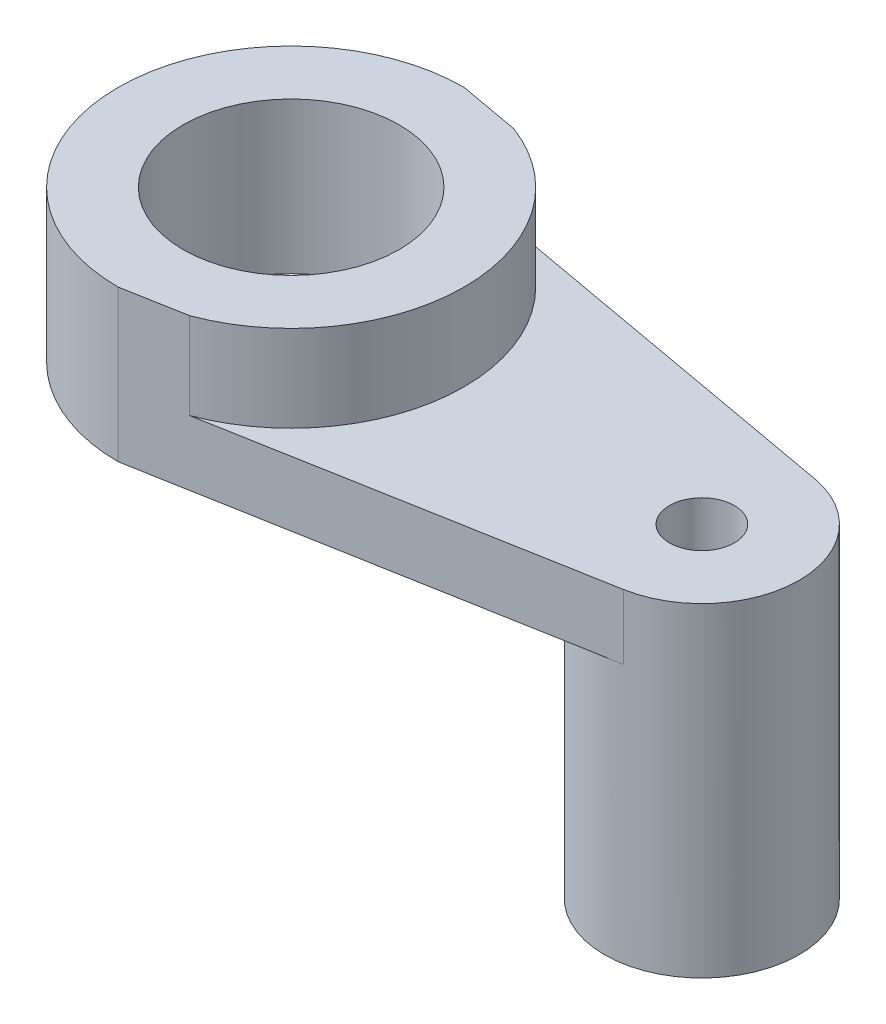
SolidWorks part; units mm, degrees
ref_plane "Front Plane" through (0, 0, 0) normal (0, 0, 1) x (1, 0, 0)
ref_plane "Top Plane" through (0, 0, 0) normal (0, 1, 0) x (1, 0, 0)
ref_plane "Right Plane" through (0, 0, 0) normal (1, 0, 0) x (0, 0, -1)
sketch "Sketch1" plane through (0, 0, 0) normal (0, 1, 0) x (1, 0, 0)
  line L0 (0, 0) -> (38, 0)
  line L1 (0, -16) -> (39.5977, -8.8571)
  line L2 (0, 16) -> (39.5977, 8.8571)
  circle A0 centre (0, 0) radius 10
  circle A1 centre (0, 0) radius 16
  circle A3 centre (38, 0) radius 9
  circle A4 centre (38, 0) radius 3
  dimension "D1" = 6
  dimension "D2" = 20
  dimension "D4" = 6
  dimension "D5" = 18
  dimension "D3" = 38
extrude "Boss-Extrude1" add sketch "Sketch1" along normal blind 14 contours L1 A1 A0 L2 region at (12.7707, 0, 8.8675)
extrude "Boss-Extrude2" add sketch "Sketch1<3>" along normal blind 6 contours A3 L2 A1 L0 | A3 L0 A1 L1 | A4 A3 region at (22.0364, 0, -6.936) region at (22.0364, 0, 6.936) region at (32.3917, 0, -6.7104)
sketch "Sketch1<3>" plane through (0, 0, 0) normal (0, 1, 0) x (1, 0, 0) same geometry as "Sketch1"
extrude "Boss-Extrude3" add sketch "Sketch1<4>" against normal blind 24 contours A4 A3 region at (32.3917, 0, -6.7104)
sketch "Sketch1<4>" plane through (0, 0, 0) normal (0, 1, 0) x (1, 0, 0) same geometry as "Sketch1"
